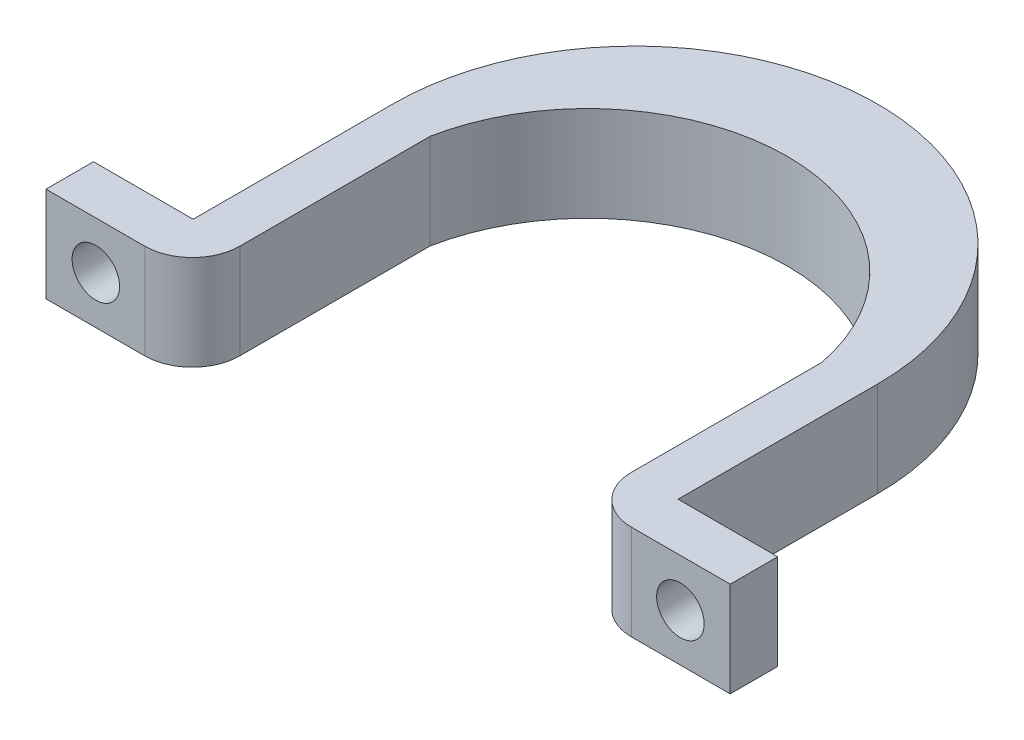
SolidWorks part; units mm, degrees
ref_plane "Front Plane" through (0, 0, 0) normal (0, 0, 1) x (1, 0, 0)
ref_plane "Top Plane" through (0, 0, 0) normal (0, 1, 0) x (1, 0, 0)
ref_plane "Right Plane" through (0, 0, 0) normal (1, 0, 0) x (0, 0, -1)
sketch "Sketch1" plane through (0, 0, 0) normal (0, 1, 0) x (1, 0, 0)
  line L0 (-759.8763, 0) -> (-36, 0) construction
  line L1 (0, -759.8763) -> (0, 37233.9375) construction
  line L2 (-36, 0) -> (-25.5147, 0) construction
  line L3 (25.5147, 0) -> (36, 0) construction
  line L4 (-36, 0) -> (-36, 5) construction
  line L5 (-36, 5) -> (-25.5147, 5) construction
  line L6 (36, 0) -> (36, 5) construction
  line L7 (36, 5) -> (25.5147, 5) construction
  line L8 (-20.608, 4.0385) -> (-20.608, -16)
  line L9 (-25.608, -21) -> (-36, -21)
  line L10 (-36, -21) -> (-36, -16)
  line L11 (-36, -16) -> (-25.5147, -16)
  line L12 (-25.5147, -16) -> (-25.5147, 5)
  line L13 (25.5147, -16) -> (25.5147, 5)
  line L14 (20.608, 4.0385) -> (20.608, -16)
  line L15 (25.608, -21) -> (36, -21)
  line L16 (36, -21) -> (36, -16)
  line L17 (36, -16) -> (25.5147, -16)
  line L18 (-36, 0) -> (-25.5147, 0) construction
  line L19 (-25.5147, 0) -> (20.608, 0) construction
  line L20 (25.5147, 0) -> (36, 0) construction
  line L21 (36, 0) -> (37233.9375, 0) construction
  line L22 (20.608, 0) -> (25.5147, 0) construction
  arc A0 (-20.608, 4.0385) -> (20.608, 4.0385) centre (0, 0) cw
  arc A1 (20.608, 4.0385) -> (25.5147, 0) centre (25.5147, 5) ccw construction
  arc A2 (-25.5147, 0) -> (-20.608, 4.0385) centre (-25.5147, 5) ccw construction
  arc A3 (-25.5147, 5) -> (25.5147, 5) centre (0, 5) cw
  arc A4 (-20.608, -16) -> (-25.608, -21) centre (-25.608, -16) cw
  arc A5 (20.608, -16) -> (25.608, -21) centre (25.608, -16) ccw
  point P13 (21, 0)
  point P16 (-21, 0)
  point P23 (0, 21)
  point P32 (-36, 2.5)
  dimension "D2" = 15
  dimension "D4" = 5
  dimension "D7" = 5
  dimension "D1" = 42
  dimension "D3" = 15
  dimension "D5" = 42
  dimension "D6" = 5
extrude "Extrude-Thin1" [suppressed] add sketch "Sketch1" along normal blind 15 thin thin type one direction wall 10
sketch "Sketch2" [suppressed] plane through (0, 0, 0) normal (0, 0, -1) x (-1, 0, 0)
  line L4 (25.5147, 0) -> (36, 0)
  line L5 (36, 0) -> (36, 15)
  line L6 (36, 15) -> (25.5147, 15)
  line L7 (25.5147, 15) -> (25.5147, 0)
  line L8 (25.5147, 0) -> (36, 0)
  line L9 (36, 0) -> (36, 15)
  line L10 (36, 15) -> (25.5147, 15)
  line L11 (25.5147, 15) -> (25.5147, 0)
  circle A0 centre (30.5181, 7.8835) radius 2.5
  circle A1 centre (-30.941, 7.8835) radius 2.5
  dimension "D2" = 5
  dimension "D1" = 0
extrude "Boss-Extrude1" add sketch "Sketch1<2>" along normal blind 10
sketch "Sketch1<2>" plane through (0, 0, 0) normal (0, 1, 0) x (1, 0, 0) same geometry as "Sketch1"
sketch "Sketch4" plane through (0, 0, 16) normal (0, 0, -1) x (-1, 0, 0)
  line L0 (25.5147, 10) -> (36, 10) construction
  line L1 (25.5147, 10) -> (36, 10) construction
  line L2 (36, 10) -> (36, 0) construction
  line L3 (36, 10) -> (36, 0) construction
  line L4 (-36, 0) -> (-25.5147, 0)
  line L5 (-25.5147, 0) -> (-25.5147, 10)
  line L6 (-25.5147, 10) -> (-36, 10)
  line L7 (-36, 10) -> (-36, 0)
  line L8 (-36, 0) -> (-25.5147, 0) construction
  line L9 (-25.5147, 0) -> (-25.5147, 10) construction
  line L10 (-25.5147, 10) -> (-36, 10) construction
  line L11 (-36, 10) -> (-36, 0) construction
  line L12 (0, 0) -> (0, 50000) construction
  line L13 (0, 4.2688) -> (0, 50004.2688) construction
  circle A0 centre (-30.7574, 5) radius 2.5
  circle A1 centre (30.7574, 5) radius 2.5
  point P9 (-30.7574, 10)
  point P10 (-36, 5)
  dimension "D2" = 5
  dimension "D1" = 0
extrude "Cut-Extrude1" cut sketch "Sketch4" against normal through all
